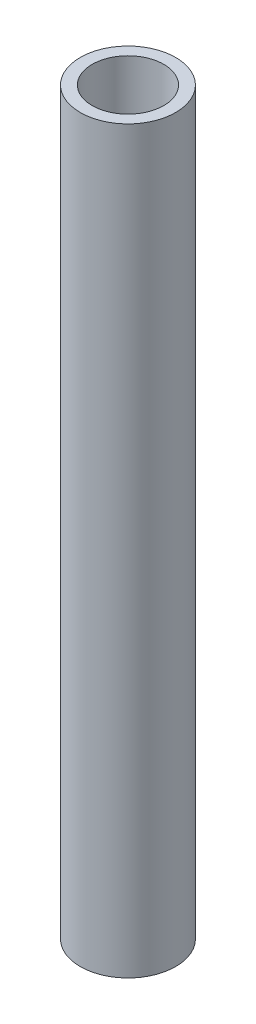
SolidWorks part; units mm, degrees
ref_plane "Front Plane" through (0, 0, 0) normal (0, 0, 1) x (1, 0, 0)
ref_plane "Top Plane" through (0, 0, 0) normal (0, 1, 0) x (1, 0, 0)
ref_plane "Right Plane" through (0, 0, 0) normal (1, 0, 0) x (0, 0, -1)
sketch "Sketch2" plane through (0, 0, 0) normal (0, 1, 0) x (1, 0, 0)
  circle A0 centre (-14.5676, 0) radius 12.7
  circle A2 centre (-14.5676, 0) radius 9.525
extrude "Boss-Extrude1" add sketch "Sketch2" along normal blind 196.85
